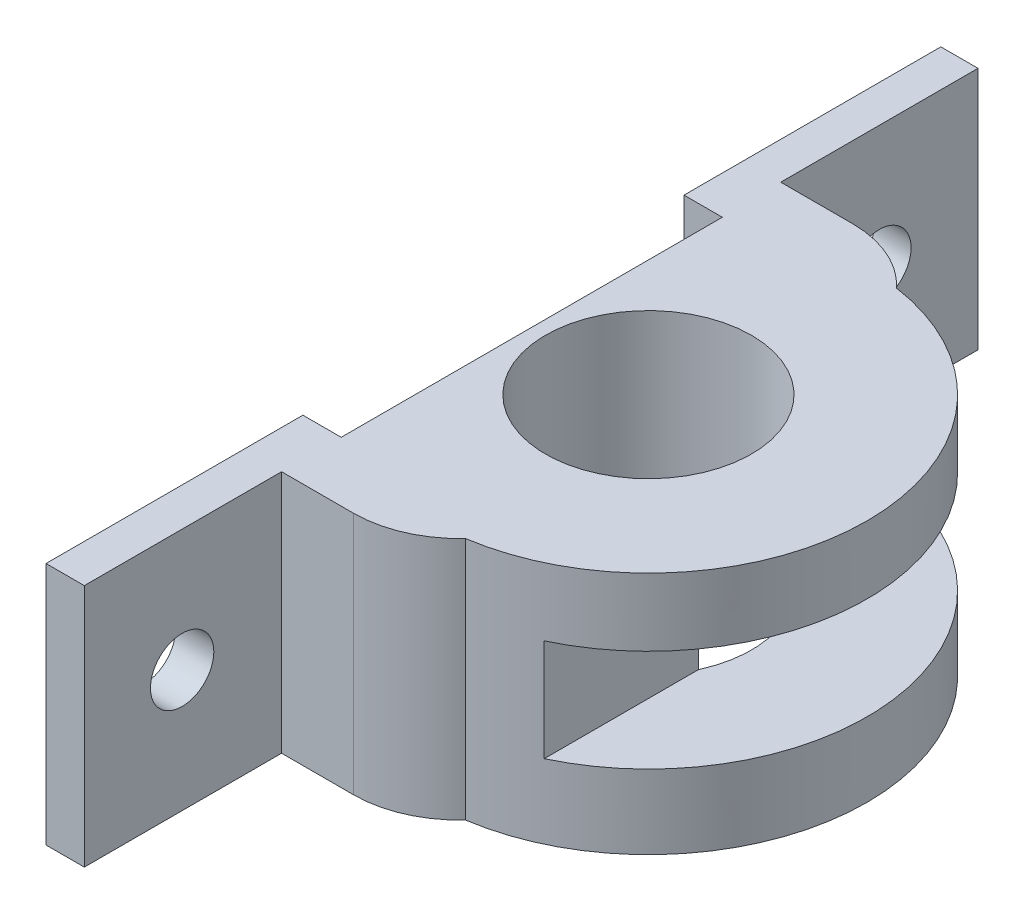
SolidWorks part; units mm, degrees
ref_plane "前基準面" through (0, 0, 0) normal (0, 0, 1) x (1, 0, 0)
ref_plane "上基準面" through (0, 0, 0) normal (0, 1, 0) x (1, 0, 0)
ref_plane "右基準面" through (0, 0, 0) normal (1, 0, 0) x (0, 0, -1)
sketch "草圖1" plane through (0, 0, 0) normal (0, 1, 0) x (1, 0, 0)
  circle A0 centre (0, 0) radius 9.68
  dimension "D1" = 19.36
extrude "伸長-薄件1" add sketch "草圖1" along normal blind 116.68 thin thin type one direction wall 11
ref_plane "平面1" through (-21, 0, 0) normal (1, 0, 0) x (0, 0, -1)
sketch "草圖11" plane through (0, 116.68, 0) normal (0, 1, 0) x (1, 0, 0)
  line L0 (-993.1634, -44.2358) -> (49006.8366, -44.2358) construction
  line L2 (35.2085, 30.7642) -> (8.2085, 30.7642)
  line L3 (35.2085, 30.7642) -> (35.2085, -119.2358)
  line L4 (35.2085, -119.2358) -> (8.2085, -119.2358)
  line L5 (8.2085, 30.7642) -> (8.2085, -119.2358)
  line L6 (35.2085, 30.7642) -> (8.2085, -119.2358) construction
  line L7 (35.2085, -119.2358) -> (8.2085, 30.7642) construction
  circle A0 centre (0, 0) radius 20.68 construction
  point P1 (21.7085, -44.2358)
  dimension "D1" = 150
  dimension "D2" = 27
  dimension "D3" = 30.7642
extrude "除料-伸長3" cut sketch "草圖11" against normal blind 40
ref_plane "平面2" through (0, 0, 21) normal (0, 0, 1) x (1, 0, 0)
sketch "草圖13" plane through (0, 0, 21) normal (0, 0, 1) x (1, 0, 0)
  line L0 (-21, -22.649) -> (-21, 22.649) construction
  line L1 (-21, 122.7847) -> (-11, 122.7847)
  line L2 (-21, 122.7847) -> (-21, -5.5603)
  line L3 (-21, -5.5603) -> (-11, -5.5603)
  line L4 (-11, 122.7847) -> (-11, -5.5603)
  dimension "D1" = 10
extrude "除料-伸長7" cut sketch "草圖13" against normal through all
sketch "草圖15" plane through (0, 0, 21) normal (0, 0, 1) x (1, 0, 0)
  line L0 (-1.3957, -883.32) -> (-1.3957, 49116.68) construction
  line L1 (8.2085, 116.68) -> (-11, 116.68) construction
  line L2 (-11, 0) -> (20.68, 0) construction
  line L3 (2.6043, 86.68) -> (-5.3957, 86.68)
  line L4 (2.6043, 86.68) -> (2.6043, 18)
  line L5 (2.6043, 18) -> (-5.3957, 18)
  line L6 (-5.3957, 86.68) -> (-5.3957, 18)
  line L7 (2.6043, 86.68) -> (-5.3957, 18) construction
  line L8 (2.6043, 18) -> (-5.3957, 86.68) construction
  point P1 (-1.3957, 52.34)
  point P5 (-1.3957, 116.68)
  dimension "D1" = 30
  dimension "D2" = 18
  dimension "D3" = 8
extrude "除料-伸長9" cut sketch "草圖15" against normal blind 48
sketch "草圖16" plane through (8.2085, 0, 0) normal (1, 0, 0) x (0, 0, -1)
  line L0 (20.68, 86.68) -> (20.68, 116.68) construction
  line L1 (5.1306, 116.68) -> (20.68, 116.68)
  line L2 (5.1306, 116.68) -> (5.1306, 96.68)
  line L3 (5.1306, 96.68) -> (20.68, 96.68)
  line L4 (20.68, 116.68) -> (20.68, 96.68)
  line L5 (-5.1306, 76.68) -> (-5.1306, 116.68) construction
  line L6 (-5.1306, 96.68) -> (-20.59, 96.68)
  line L7 (-5.1306, 96.68) -> (-5.1306, 116.68)
  line L8 (-5.1306, 116.68) -> (-20.59, 116.68)
  line L9 (-20.59, 96.68) -> (-20.59, 116.68)
  line L10 (-17.5118, 116.68) -> (-20.68, 116.68) construction
  dimension "D1" = 20
extrude "填料-伸長4" add sketch "草圖16" against normal blind 19.2
sketch "草圖17" plane through (0, 116.68, 0) normal (0, 1, 0) x (1, 0, 0)
  line L0 (-1009.59, 0) -> (48990.41, 0) construction
  line L1 (8.2085, 20.68) -> (8.2085, 5.1306) construction
  line L2 (8.2085, 6.97) -> (-11, 6.97)
  line L3 (8.2085, 6.97) -> (8.2085, -7.06)
  line L4 (8.2085, -7.06) -> (-11, -7.06)
  line L5 (-11, 6.97) -> (-11, -7.06)
  line L6 (-11, -17.5118) -> (-11, 17.5118) construction
  line L7 (-10.9915, -20.59) -> (-1.9273, -20.59) construction
  arc A0 (-8.2085, 5.1306) -> (-8.2085, -5.1306) centre (0, 0) ccw construction
  point P6 (-9.68, 0)
  dimension "D1" = 14.03
  dimension "D2" = 13.53
extrude "除料-伸長10" cut sketch "草圖17" against normal blind 20.2
sketch "草圖18" plane through (0, 0, 0) normal (0, -1, 0) x (1, 0, 0)
  circle A0 centre (0, 0) radius 9.59
extrude "除料-伸長11" cut sketch "草圖18" against normal through all
sketch "草圖21" plane through (0, 0, -20.68) normal (0, 0, -1) x (-1, 0, 0)
  line L0 (1.3915, 96.68) -> (1.3915, 105.73) construction
  line L1 (0, 96.68) -> (10.9915, 96.68) construction
  line L2 (1.3915, 105.73) -> (1.3915, 108.73) construction
  circle A0 centre (1.3915, 108.73) radius 2.985
  dimension "D3" = 5.97
  dimension "D1" = 9.05
  dimension "D2" = 3
extrude "除料-伸長12" cut sketch "草圖21" against normal blind 55.2
sketch "草圖23" plane through (0, 0, -20.68) normal (0, 0, -1) x (-1, 0, 0)
  line L0 (1.3915, 105.745) -> (1.3915, -11.785) construction
  circle A0 centre (1.3915, 108.73) radius 2.985 construction
  dimension "D1" = 117.53
sketch "草圖24" plane through (0, 0, 0) normal (0, -1, 0) x (1, 0, 0)
  circle A0 centre (0, 0) radius 9.59
extrude "伸長-薄件2" add sketch "草圖24" along normal blind 55.2 thin thin type one direction wall 11
sketch "草圖25" plane through (0, 0, 21) normal (0, 0, 1) x (1, 0, 0)
  line L0 (-1.3915, -11.785) -> (22.6124, -11.785)
  line L1 (22.6124, -11.785) -> (22.6124, -63.8733)
  line L2 (-22.7495, -63.8733) -> (22.6124, -63.8733)
  line L3 (-22.7495, -63.8733) -> (-22.7495, -11.785)
  line L4 (-22.7495, -11.785) -> (-1.3915, -11.785)
extrude "除料-伸長13" cut sketch "草圖25" against normal blind 55.2
sketch "草圖26" plane through (0, 0, 0) normal (0, 1, 0) x (1, 0, 0)
  line L0 (-21, -22.649) -> (-21, 22.649) construction
  line L1 (-10.9915, 20.68) -> (-21, 20.68)
  line L2 (-10.9915, 20.68) -> (-10.9915, -21)
  line L3 (-10.9915, -21) -> (-21, -21)
  line L4 (-21, 20.68) -> (-21, -21)
  line L5 (-17.6, -21) -> (17.6, -21) construction
extrude "除料-伸長15" cut sketch "草圖26" against normal blind 55.2
ref_plane "平面3" through (21, 0, 0) normal (1, 0, 0) x (0, 0, -1)
sketch "草圖27" plane through (21, 0, 0) normal (1, 0, 0) x (0, 0, -1)
  line L0 (0, -923.32) -> (0, 49076.68) construction
  line L1 (5.1306, 76.68) -> (-5.1306, 76.68) construction
  line L2 (18.9811, 76.68) -> (-18.9811, 76.68) construction
  line L3 (-5, 61.68) -> (5, 61.68)
  line L4 (-5, 61.68) -> (-5, 21.68)
  line L5 (-5, 21.68) -> (5, 21.68)
  line L6 (5, 61.68) -> (5, 21.68)
  line L7 (-5, 61.68) -> (5, 21.68) construction
  line L8 (-5, 21.68) -> (5, 61.68) construction
  point P1 (0, 41.68)
  point P5 (0, 76.68)
  dimension "D1" = 15
  dimension "D2" = 40
  dimension "D3" = 10
extrude "除料-伸長16" cut sketch "草圖27" against normal blind 55.2
sketch "草圖28" plane through (21, 0, 0) normal (1, 0, 0) x (0, 0, -1)
  line L1 (-22.4403, 4.804) -> (22.4403, 4.804)
  line L2 (-22.4403, 4.804) -> (-22.4403, -4.804)
  line L3 (-22.4403, -4.804) -> (22.4403, -4.804)
  line L4 (22.4403, 4.804) -> (22.4403, -4.804)
  line L5 (-22.4403, 4.804) -> (22.4403, -4.804) construction
  line L6 (-22.4403, -4.804) -> (22.4403, 4.804) construction
  point P0 (0, 0)
extrude "除料-伸長17" cut sketch "草圖28" against normal blind 12.2
sketch "草圖35" plane through (-10.9915, 0, 0) normal (-1, 0, 0) x (0, 0, 1)
  line L0 (20.59, 116.68) -> (20.59, 96.68)
  line L1 (20.59, 96.68) -> (7.06, 96.68)
  line L2 (7.06, 96.68) -> (7.06, 116.68)
  line L3 (7.06, 116.68) -> (20.59, 116.68)
extrude "填料-伸長10" add sketch "草圖35" along normal blind 15
sketch "草圖36" plane through (-10.9915, 0, 0) normal (-1, 0, 0) x (0, 0, 1)
  line L0 (-20.68, 116.68) -> (-6.97, 116.68)
  line L1 (-6.97, 116.68) -> (-6.97, 96.48)
  line L2 (-6.97, 96.48) -> (-20.68, 96.68)
  line L3 (-20.68, 96.68) -> (-20.68, 116.68)
extrude "填料-伸長11" add sketch "草圖36" along normal blind 15
sketch "草圖37" plane through (0, 0, 20.59) normal (0, 0, 1) x (1, 0, 0)
  line L0 (-25.9915, 96.68) -> (-1.9273, 96.68) construction
  line L1 (-25.9915, 116.68) -> (-16.9915, 116.68)
  line L2 (-25.9915, 116.68) -> (-25.9915, 96.68)
  line L3 (-25.9915, 96.68) -> (-16.9915, 96.68)
  line L4 (-16.9915, 116.68) -> (-16.9915, 96.68)
  dimension "D1" = 9
extrude "填料-伸長12" add sketch "草圖37" along normal blind 20
sketch "草圖38" plane through (0, 0, -20.68) normal (0, 0, -1) x (-1, 0, 0)
  line L0 (25.9915, 116.68) -> (-8.2085, 116.68) construction
  line L1 (25.9915, 96.68) -> (16.9915, 96.68)
  line L2 (25.9915, 96.68) -> (25.9915, 116.68)
  line L3 (25.9915, 116.68) -> (16.9915, 116.68)
  line L4 (16.9915, 96.68) -> (16.9915, 116.68)
  dimension "D1" = 9
extrude "填料-伸長13" add sketch "草圖38" along normal blind 20
sketch "草圖42" plane through (-16.9915, 0, 0) normal (1, 0, 0) x (0, 0, -1)
  line L0 (30.68, -903.32) -> (30.68, 49096.68) construction
  line L1 (40.68, 96.68) -> (20.68, 96.68) construction
  line L2 (-959.32, 106.68) -> (49040.68, 106.68) construction
  line L3 (40.68, 116.68) -> (40.68, 96.68) construction
  line L4 (-30.59, -903.32) -> (-30.59, 49096.68) construction
  line L5 (-40.59, 96.68) -> (-20.59, 96.68) construction
  circle A0 centre (30.68, 106.5544) radius 2.985
  circle A1 centre (-30.3956, 106.68) radius 2.985
  point P5 (30.68, 96.68)
  point P10 (40.68, 106.68)
  point P15 (-30.59, 96.68)
  dimension "D1" = 5.97
  dimension "D2" = 5.97
extrude "除料-伸長21" cut sketch "草圖42" against normal blind 20
sketch "草圖43" plane through (0, 116.68, 0) normal (0, 1, 0) x (1, 0, 0)
  line L0 (-11, 6.97) -> (-10.9915, 20.68)
  line L1 (-10.9915, 20.68) -> (-10.9915, 48.0968)
  line L2 (-10.9915, 48.0968) -> (-28.2748, 48.0968)
  line L3 (-28.2748, 48.0968) -> (-28.2748, -43.2705)
  line L4 (-28.2748, -43.2705) -> (-11, -43.2705)
  line L5 (-11, -43.2705) -> (-11, 6.97)
extrude "除料-伸長23" cut sketch "草圖43" against normal through all
sketch "草圖45" plane through (0, 0, 20.59) normal (0, 0, 1) x (1, 0, 0)
  line L0 (-11, 96.68) -> (-1.9273, 96.68) construction
  line L1 (-11, 116.68) -> (-8, 116.68)
  line L2 (-11, 116.68) -> (-11, 96.68)
  line L3 (-11, 96.68) -> (-8, 96.68)
  line L4 (-8, 116.68) -> (-8, 96.68)
  dimension "D1" = 3
extrude "填料-伸長14" add sketch "草圖45" along normal blind 30
sketch "草圖46" plane through (0, 0, -20.68) normal (0, 0, -1) x (-1, 0, 0)
  line L0 (0, 96.68) -> (10.9915, 96.68) construction
  line L1 (10.9915, 116.68) -> (7.9915, 116.68)
  line L2 (10.9915, 116.68) -> (10.9915, 96.68)
  line L3 (10.9915, 96.68) -> (7.9915, 96.68)
  line L4 (7.9915, 116.68) -> (7.9915, 96.68)
  dimension "D1" = 3
extrude "填料-伸長15" add sketch "草圖46" along normal blind 30
sketch "草圖47" plane through (-11, 0, 0) normal (-1, 0, 0) x (0, 0, 1)
  line L0 (50.59, 116.68) -> (7.06, 116.68) construction
  line L1 (50.59, 96.68) -> (17.5118, 96.68)
  line L2 (50.59, 96.68) -> (50.59, 116.68)
  line L3 (50.59, 116.68) -> (17.5118, 116.68)
  line L4 (17.5118, 96.68) -> (17.5118, 116.68)
extrude "填料-伸長16" add sketch "草圖47" along normal blind 50
sketch "草圖48" plane through (-10.9915, 0, 0) normal (-1, 0, 0) x (0, 0, 1)
  line L1 (-50.68, 116.68) -> (-20.68, 116.68)
  line L2 (-50.68, 116.68) -> (-50.68, 96.68)
  line L3 (-50.68, 96.68) -> (-20.68, 96.68)
  line L4 (-20.68, 116.68) -> (-20.68, 96.68)
extrude "填料-伸長17" add sketch "草圖48" along normal blind 50
sketch "草圖50" plane through (0, 0, 17.5118) normal (0, 0, -1) x (-1, 0, 0)
  line L0 (11, 96.68) -> (11, 116.68)
  line L1 (11, 116.68) -> (61, 116.68)
  line L2 (61, 116.68) -> (61, 96.68)
  line L3 (61, 96.68) -> (11, 96.68)
extrude "填料-伸長18" add sketch "草圖50" along normal blind 1
sketch "草圖51" plane through (0, 0, -20.68) normal (0, 0, 1) x (1, 0, 0)
  line L0 (-10.9915, 116.68) -> (-10.9915, 96.68)
  line L1 (-10.9915, 96.68) -> (-60.9915, 96.68)
  line L2 (-60.9915, 96.68) -> (-60.9915, 116.68)
  line L3 (-60.9915, 116.68) -> (-10.9915, 116.68)
extrude "填料-伸長19" add sketch "草圖51" along normal blind 1
sketch "草圖52" plane through (0, 116.68, 0) normal (0, 1, 0) x (1, 0, 0)
  line L0 (-34.4915, -949.32) -> (-34.4915, 49050.68) construction
  line L1 (-60.9915, 50.68) -> (-7.9915, 50.68) construction
  line L2 (-1007.9915, 35.68) -> (48992.0085, 35.68) construction
  line L3 (-7.9915, 50.68) -> (-7.9915, 20.68) construction
  line L4 (-60.9915, 19.68) -> (-60.9915, 50.68) construction
  line L5 (-7.9915, 50.68) -> (-60.9915, 50.68)
  line L6 (-7.9915, 50.68) -> (-7.9915, 36.68)
  line L7 (-7.9915, 36.68) -> (-60.9915, 36.68)
  line L8 (-60.9915, 50.68) -> (-60.9915, 36.68)
  point P5 (-34.4915, 50.68)
  point P10 (-7.9915, 35.68)
  dimension "D1" = 14
extrude "除料-伸長24" cut sketch "草圖52" against normal through all
sketch "草圖53" plane through (0, 116.68, 0) normal (0, 1, 0) x (1, 0, 0)
  line L0 (-61, -50.59) -> (-61, -16.5118) construction
  line L1 (-8, -50.59) -> (-61, -50.59)
  line L2 (-8, -50.59) -> (-8, -36.59)
  line L3 (-8, -36.59) -> (-61, -36.59)
  line L4 (-61, -50.59) -> (-61, -36.59)
  dimension "D1" = 14
extrude "除料-伸長25" cut sketch "草圖53" against normal through all
sketch "草圖54" plane through (0, 116.68, 0) normal (0, 1, 0) x (1, 0, 0)
  line L0 (-60.9915, 36.68) -> (-7.9915, 36.68) construction
  line L1 (-61, -36.59) -> (-21, -36.59)
  line L2 (-61, -36.59) -> (-61, 36.68)
  line L3 (-61, 36.68) -> (-21, 36.68)
  line L4 (-21, -36.59) -> (-21, 36.68)
  dimension "D1" = 40
extrude "除料-伸長26" cut sketch "草圖54" against normal through all
sketch "草圖55" plane through (0, 116.68, 0) normal (0, 1, 0) x (1, 0, 0)
  line L0 (-15.0276, -36.59) -> (-15.0276, -16.5118) construction
  line L1 (-8, -36.59) -> (-21, -36.59) construction
  line L2 (-21, -16.5118) -> (-11, -16.5118) construction
  line L3 (-13.4574, 19.68) -> (-13.4574, 39.76) construction
  line L4 (-10.9921, 19.68) -> (-21, 19.68) construction
  dimension "D1" = 20.08
sketch "草圖56" plane through (0, 0, -36.68) normal (0, 0, -1) x (-1, 0, 0)
  line L1 (7.9915, 96.68) -> (21, 96.68)
  line L2 (7.9915, 96.68) -> (7.9915, 116.68)
  line L3 (7.9915, 116.68) -> (21, 116.68)
  line L4 (21, 96.68) -> (21, 116.68)
extrude "填料-伸長21" add sketch "草圖56" along normal blind 3.08
ref_plane "平面4" through (0, 0, 50) normal (0, 0, 1) x (1, 0, 0)
sketch "草圖60" plane through (0, 116.68, 0) normal (0, 1, 0) x (1, 0, 0)
  line L0 (-21, 39.76) -> (-7.9915, 39.76) construction
  line L1 (-21, -36.59) -> (-14.4957, -36.59)
  line L2 (-21, -36.59) -> (-21, 39.76)
  line L3 (-21, 39.76) -> (-14.4957, 39.76)
  line L4 (-14.4957, -36.59) -> (-14.4957, 39.76)
extrude "除料-伸長30" cut sketch "草圖60" against normal through all
sketch "草圖61" plane through (0, 116.68, 0) normal (0, 1, 0) x (1, 0, 0)
  line L0 (1.9273, -20.59) -> (1.9273, -22.3991)
  line L1 (1.9273, -22.3991) -> (-2.1742, -21.4215)
  line L2 (-2.1742, -21.4215) -> (-2.1742, -20.59)
  line L3 (-8, -20.59) -> (-1.9273, -20.59) construction
  line L4 (-2.1742, -20.59) -> (1.9273, -20.59)
extrude "除料-伸長32" cut sketch "草圖61" against normal blind 20
sketch "草圖64" plane through (0, 116.68, 0) normal (0, 1, 0) x (1, 0, 0)
  line L1 (-8, -20.59) -> (8.2085, -20.59)
  line L2 (-8, -20.59) -> (-8, -20.68)
  line L3 (-8, -20.68) -> (8.2085, -20.68)
  line L4 (8.2085, -20.59) -> (8.2085, -20.68)
  dimension "D1" = 0.09
extrude "填料-伸長22" add sketch "草圖64" against normal blind 20
sketch "草圖65" plane through (0, 116.68, 0) normal (0, 1, 0) x (1, 0, 0)
  line L0 (-11, 6.97) -> (-10.9921, 19.68) construction
  line L1 (-11, -7.06) -> (-11, -16.5118) construction
  line L2 (-14.4957, -36.59) -> (-14.4957, -16.5118) construction
  line L3 (-11, -16.5118) -> (-14.4957, -16.5118)
  line L4 (-11, -16.5118) -> (-11, -19.7718)
  line L5 (-11, -19.7718) -> (-14.4957, -19.7718)
  line L6 (-14.4957, -16.5118) -> (-14.4957, -19.7718)
  dimension "D1" = 12.71
  dimension "D2" = 9.4518
  dimension "D3" = 3.26
extrude "除料-伸長33" cut sketch "草圖65" against normal through all
sketch "草圖66" plane through (0, 96.48, 0) normal (0, 1, 0) x (1, 0, 0)
  line L0 (-1011, -0.045) -> (48989, -0.045) construction
  line L1 (-11, 6.97) -> (-11, -7.06) construction
  line L2 (-12.9194, -0.045) -> (-12.9194, 17.905) construction
  line L3 (-12.9194, -0.045) -> (-12.9194, -17.995) construction
  line L4 (-11, -19.7718) -> (-11, -7.06) construction
  line L5 (-14.4957, -19.7718) -> (-11, -19.7718)
  line L6 (-14.4957, -19.7718) -> (-14.4957, -17.995)
  line L7 (-14.4957, -17.995) -> (-11, -17.995)
  line L8 (-11, -19.7718) -> (-11, -17.995)
  line L10 (-10.9921, 19.68) -> (-14.4957, 19.68)
  line L11 (-10.9921, 19.68) -> (-10.9921, 17.905)
  line L12 (-10.9921, 17.905) -> (-14.4957, 17.905)
  line L13 (-14.4957, 19.68) -> (-14.4957, 17.905)
  point P5 (-11, -0.045)
  dimension "D1" = 17.95
  dimension "D2" = 17.95
extrude "填料-伸長23" add sketch "草圖66" along normal blind 20.2
sketch "草圖68" plane through (0, 116.68, 0) normal (0, 1, 0) x (1, 0, 0)
  line L0 (-10.9932, 17.905) -> (-10.9932, 39.76) construction
  line L1 (-14.4957, 39.76) -> (-7.9915, 39.76) construction
  line L2 (-14.4957, 17.905) -> (-14.4957, 39.76) construction
  line L3 (-7.9915, 39.76) -> (-14.4957, 39.76)
  line L4 (-7.9915, 39.76) -> (-7.9915, 36.1)
  line L5 (-7.9915, 36.1) -> (-14.4957, 36.1)
  line L6 (-14.4957, 39.76) -> (-14.4957, 36.1)
  dimension "D1" = 3.66
extrude "除料-伸長34" cut sketch "草圖68" against normal blind 20
sketch "草圖69" plane through (-7.9915, 0, 0) normal (1, 0, 0) x (0, 0, -1)
  line L0 (28.39, -903.32) -> (28.39, 49096.68) construction
  line L1 (36.1, 96.68) -> (20.68, 96.68) construction
  line L2 (-28.635, -903.32) -> (-28.635, 49096.68) construction
  line L3 (-36.59, 96.68) -> (-20.68, 96.68) construction
  line L4 (-963.9, 106.68) -> (49036.1, 106.68) construction
  line L5 (36.1, 96.68) -> (36.1, 116.68) construction
  circle A0 centre (28.39, 106.68) radius 2.985
  circle A1 centre (-28.635, 106.68) radius 2.985
  point P5 (28.39, 96.68)
  point P10 (-28.635, 96.68)
  point P15 (36.1, 106.68)
  dimension "D1" = 5.97
  dimension "D2" = 5.97
extrude "除料-伸長35" cut sketch "草圖69" against normal through all
sketch "草圖70" plane through (0, 0, 20.59) normal (0, 0, -1) x (-1, 0, 0)
  circle A0 centre (1.3915, 108.73) radius 2.985
  dimension "D1" = 5.97
extrude "除料-伸長36" cut sketch "草圖70" against normal through all
sketch "草圖71" plane through (0, 0, 50) normal (0, 0, 1) x (1, 0, 0)
  line L1 (-16.2413, 123.1465) -> (21.764, 123.1465)
  line L2 (-16.2413, 123.1465) -> (-16.2413, 11.1806)
  line L3 (-16.2413, 11.1806) -> (21.764, 11.1806)
  line L4 (21.764, 123.1465) -> (21.764, 11.1806)
extrude "除料-伸長37" cut sketch "草圖71" against normal through all
sketch "草圖72" plane through (0, -11.785, 0) normal (0, -1, 0) x (1, 0, 0)
  circle A0 centre (0, 0) radius 9.7
  dimension "D1" = 19.4
extrude "除料-伸長38" cut sketch "草圖72" against normal through all
sketch "草圖77" plane through (0, 11.1806, 0) normal (0, 1, 0) x (1, 0, 0)
  circle A0 centre (0, 0) radius 20.59
  dimension "D1" = 41.18
extrude "除料-伸長-薄件2" cut sketch "草圖77" against normal blind 22 thin thin type one direction wall 10
sketch "草圖78" plane through (-11, 0, 0) normal (-1, 0, 0) x (0, 0, 1)
  line L1 (17.4054, 11.1806) -> (-17.4108, 11.1806)
  line L2 (17.4054, 11.1806) -> (17.4054, -11.785)
  line L3 (17.4054, -11.785) -> (-17.4108, -11.785)
  line L4 (-17.4108, 11.1806) -> (-17.4108, -11.785)
extrude "填料-伸長26" add sketch "草圖78" along normal blind 0.1
sketch "草圖80" plane through (0, -11.785, 0) normal (0, -1, 0) x (1, 0, 0)
  line L1 (-11.1, -17.4108) -> (-14, -17.4108)
  line L2 (-11.1, -17.4108) -> (-11.1, -23.5595)
  line L3 (-11.1, -23.5595) -> (-14, -23.5595)
  line L4 (-14, -17.4108) -> (-14, -23.5595)
extrude "填料-伸長28" add sketch "草圖80" against normal blind 23.1 separate body
sketch "草圖81" plane through (-11.1, 0, 0) normal (1, 0, 0) x (0, 0, -1)
  line L0 (17.4108, -11.785) -> (23.5595, -11.785)
  line L1 (23.5595, -11.785) -> (23.5595, 11.315)
  line L2 (23.5595, 11.315) -> (17.4108, 11.315)
  line L3 (17.4108, 11.315) -> (17.4108, -11.785)
extrude "填料-伸長29" add sketch "草圖81" along normal blind 14.1
sketch "草圖82" plane through (3, 0, 0) normal (1, 0, 0) x (0, 0, -1)
  line L0 (17.4108, 11.1806) -> (17.4108, 11.315)
  line L1 (17.4108, 11.315) -> (23.5595, 11.315)
  line L2 (23.5595, 11.315) -> (23.5595, 11.1806)
  line L3 (23.5595, -11.785) -> (23.5595, 11.315) construction
  line L4 (23.5595, 11.1806) -> (17.4108, 11.1806)
extrude "除料-伸長39" cut sketch "草圖82" against normal blind 19.1
sketch "草圖83" plane through (0, 0, -17.4108) normal (0, 0, 1) x (1, 0, 0)
  line L1 (-11.1, 11.1806) -> (-14, 11.1806)
  line L2 (-11.1, 11.1806) -> (-11.1, -11.785)
  line L3 (-11.1, -11.785) -> (-14, -11.785)
  line L4 (-14, 11.1806) -> (-14, -11.785)
extrude "填料-伸長30" add sketch "草圖83" against normal blind 19.1
fillet "圓角1" radius 10 1 edges at (3, -0.3022, -23.5595)
sketch "草圖84" plane through (0, -11.785, 0) normal (0, -1, 0) x (-1, 0, 0)
  line L1 (11.1, 17.4108) -> (14.6, 17.4108)
  line L2 (11.1, 17.4108) -> (11.1, 36.5108)
  line L3 (11.1, 36.5108) -> (14.6, 36.5108)
  line L4 (14.6, 17.4108) -> (14.6, 36.5108)
  dimension "D1" = 3.5
extrude "填料-伸長31" add sketch "草圖84" against normal blind 23.1
sketch "草圖85" plane through (0, -11.785, 0) normal (0, -1, 0) x (1, 0, 0)
  line L0 (-11.1, -17.4108) -> (-11.1, -35.9908) construction
  line L1 (-11.1, -36.5108) -> (-11.1, -23.5595) construction
  line L3 (-11.1, -35.9908) -> (-14.6, -35.9908)
  line L4 (-11.1, -35.9908) -> (-11.1, -36.5108)
  line L5 (-11.1, -36.5108) -> (-14.6, -36.5108)
  line L6 (-14.6, -35.9908) -> (-14.6, -36.5108)
  dimension "D1" = 18.58
extrude "除料-伸長40" cut sketch "草圖85" against normal through all
sketch "草圖86" plane through (0, 0, -17.4108) normal (0, 0, 1) x (1, 0, 0)
  line L1 (-11.1, 11.1806) -> (-14.6, 11.1806)
  line L2 (-11.1, 11.1806) -> (-11.1, -11.785)
  line L3 (-11.1, -11.785) -> (-14.6, -11.785)
  line L4 (-14.6, 11.1806) -> (-14.6, -11.785)
extrude "填料-伸長32" add sketch "草圖86" along normal blind 62.1
sketch "草圖87" plane through (0, -11.785, 0) normal (0, -1, 0) x (1, 0, 0)
  line L0 (-14.6, 44.6892) -> (-14.6, -35.9908) construction
  line L1 (-10.9915, -17.4108) -> (-14.6, -17.4108)
  line L2 (-10.9915, -17.4108) -> (-10.9915, 17.4054)
  line L3 (-10.9915, 17.4054) -> (-14.6, 17.4054)
  line L4 (-14.6, -17.4108) -> (-14.6, 17.4054)
extrude "除料-伸長41" cut sketch "草圖87" against normal blind 62.1
sketch "草圖89" plane through (0, -11.785, 0) normal (0, -1, 0) x (1, 0, 0)
  line L0 (-10.9915, 17.4108) -> (-10.9915, 23.5608) construction
  line L1 (-11.1, 44.6892) -> (-11.1, 17.4054) construction
  line L2 (-11.1, 23.5608) -> (-10.9915, 23.5608)
  line L3 (-11.1, 23.5608) -> (-11.1, 17.4108)
  line L4 (-11.1, 17.4108) -> (-10.9915, 17.4108)
  line L5 (-10.9915, 23.5608) -> (-10.9915, 17.4108)
  dimension "D1" = 6.15
extrude "填料-伸長33" add sketch "草圖89" against normal blind 23.1
sketch "草圖90" plane through (0, 0, 23.5608) normal (0, 0, 1) x (1, 0, 0)
  line L0 (-11, 11.1806) -> (-11.1, 11.1806)
  line L1 (-11.1, 11.1806) -> (-11.1, -11.785)
  line L2 (-11.1, -11.785) -> (-10.9915, -11.785)
  line L3 (-10.9915, -11.785) -> (-10.9915, 11.1806)
  line L4 (-10.9915, 11.1806) -> (-11, 11.1806)
extrude "填料-伸長34" add sketch "草圖90" along normal blind 22.1
sketch "草圖91" plane through (-11.1, 0, 0) normal (-1, 0, 0) x (0, 0, 1)
  line L1 (45.6608, -11.785) -> (44.6892, -11.785)
  line L2 (45.6608, -11.785) -> (45.6608, 11.1806)
  line L3 (45.6608, 11.1806) -> (44.6892, 11.1806)
  line L4 (44.6892, -11.785) -> (44.6892, 11.1806)
extrude "除料-伸長42" cut sketch "草圖91" against normal blind 22.1
sketch "草圖93" plane through (0, -11.785, 0) normal (0, -1, 0) x (1, 0, 0)
  line L0 (-10.9915, 17.4108) -> (-10.9915, 23.5608) construction
  line L1 (-10.9915, 17.4108) -> (-10.9915, 44.6892) construction
  dimension "D1" = 6.15
sketch "草圖94" plane through (-10.9915, 0, 0) normal (1, 0, 0) x (0, 0, -1)
  line L0 (-23.5608, -11.785) -> (-23.5608, 11.1806) construction
  line L1 (-17.4108, -11.785) -> (-23.5608, -11.785) construction
sketch "草圖95" plane through (-10.9915, 0, 0) normal (1, 0, 0) x (0, 0, -1)
  line L1 (-23.5608, 11.1806) -> (-17.4108, 11.1806)
  line L2 (-17.4108, 11.315) -> (-17.4108, -11.785) construction
  line L3 (-17.4108, 11.1806) -> (-17.4108, -11.785)
  line L4 (-17.4108, -11.785) -> (-23.5608, -11.785)
  line L5 (-23.5608, -11.785) -> (-23.5608, 11.1806)
extrude "填料-伸長35" add sketch "草圖95" along normal blind 14.1
fillet "圓角2" radius 10 1 edges at (3.1085, -0.3022, 23.5608)
sketch "草圖96" plane through (0, -11.785, 0) normal (0, -1, 0) x (1, 0, 0)
  line L0 (-10.9915, 23.5608) -> (-10.9915, 42.1408) construction
  line L1 (-10.9915, 23.5608) -> (-10.9915, 44.6892) construction
  line L3 (-10.9915, 42.1408) -> (-14.6, 42.1408)
  line L4 (-10.9915, 42.1408) -> (-10.9915, 44.6892)
  line L5 (-10.9915, 44.6892) -> (-14.6, 44.6892)
  line L6 (-14.6, 42.1408) -> (-14.6, 44.6892)
  dimension "D1" = 18.58
extrude "除料-伸長43" cut sketch "草圖96" against normal through all
sketch "草圖97" plane through (0, -11.785, 0) normal (0, -1, 0) x (1, 0, 0)
  line L0 (-11.1, -23.5595) -> (-11.1, -42.1395) construction
  line L2 (-14.6, -35.9908) -> (-11.1, -35.9908)
  line L3 (-14.6, -35.9908) -> (-14.6, -42.1395)
  line L4 (-14.6, -42.1395) -> (-11.1, -42.1395)
  line L5 (-11.1, -35.9908) -> (-11.1, -42.1395)
  dimension "D1" = 18.58
extrude "填料-伸長36" add sketch "草圖97" against normal blind 23.1
sketch "草圖98" plane through (-11.1, 0, 0) normal (1, 0, 0) x (0, 0, -1)
  line L0 (17.4108, 11.1806) -> (17.4108, 11.315)
  line L1 (17.4108, 11.315) -> (22.1983, 11.315)
  line L2 (42.1395, 11.315) -> (17.4108, 11.315) construction
  line L3 (22.1983, 11.315) -> (38.4617, 11.315)
  line L4 (38.4617, 11.315) -> (42.1395, 11.315)
  line L5 (42.1395, 11.315) -> (42.1395, 11.1806)
  line L6 (42.1395, 11.315) -> (42.1395, -11.785) construction
  line L7 (42.1395, 11.1806) -> (17.4108, 11.1806)
extrude "除料-伸長44" cut sketch "草圖98" against normal blind 23.1
sketch "草圖99" plane through (-10.9915, 0, 0) normal (1, 0, 0) x (0, 0, -1)
  line L1 (-23.5608, 11.1806) -> (-17.4108, 11.1806)
  line L2 (-23.5608, 11.1806) -> (-23.5608, 11.315)
  line L3 (-23.5608, 11.315) -> (-17.4108, 11.315)
  line L4 (-17.4108, 11.1806) -> (-17.4108, 11.315)
extrude "除料-伸長45" cut sketch "草圖99" against normal blind 23.1
sketch "草圖100" plane through (-10.9915, 0, 0) normal (1, 0, 0) x (0, 0, -1)
  line L0 (-1042.1408, -0.3022) -> (48957.8592, -0.3022) construction
  line L1 (-42.1408, 11.1806) -> (-42.1408, -11.785) construction
  line L2 (-32.8508, -988.8194) -> (-32.8508, 49011.1806) construction
  line L3 (-42.1408, 11.1806) -> (-23.5608, 11.1806) construction
  line L4 (32.8495, -988.8194) -> (32.8495, 49011.1806) construction
  line L5 (23.5595, 11.1806) -> (42.1395, 11.1806) construction
  point P5 (-42.1408, -0.3022)
  point P10 (-32.8508, 11.1806)
  point P15 (32.8495, 11.1806)
sketch "草圖101" plane through (-10.9915, 0, 0) normal (1, 0, 0) x (0, 0, -1)
  line L0 (-201042.1408, -0.3022) -> (248957.8592, -0.3022) construction
  line L1 (32.8495, -200988.8194) -> (32.8495, 249011.1806) construction
  circle A0 centre (-32.9287, -0.3022) radius 2.985
  circle A1 centre (32.8495, -0.3022) radius 2.985
  dimension "D1" = 5.97
  dimension "D2" = 5.97
extrude "除料-伸長46" cut sketch "草圖101" against normal blind 23.1
sketch "草圖102" plane through (0, 11.1806, 0) normal (0, 1, 0) x (1, 0, 0)
  line L0 (-14.6, 42.1395) -> (-14.6, 17.4108) construction
  line L1 (-10.9915, 17.4108) -> (-14.6, 17.4108)
  line L2 (-10.9915, 17.4108) -> (-10.9915, 17.9508)
  line L3 (-10.9915, 17.9508) -> (-14.6, 17.9508)
  line L4 (-14.6, 17.4108) -> (-14.6, 17.9508)
  line L5 (-14.6, -42.1408) -> (-14.6, -17.4054) construction
  line L6 (-10.9915, -17.4108) -> (-14.6, -17.4108)
  line L7 (-10.9915, -17.4108) -> (-10.9915, -17.9508)
  line L8 (-10.9915, -17.9508) -> (-14.6, -17.9508)
  line L9 (-14.6, -17.4108) -> (-14.6, -17.9508)
  dimension "D1" = 0.54
  dimension "D2" = 0.54
sketch "草圖103" plane through (0, 11.1806, 0) normal (0, 1, 0) x (1, 0, 0)
  line L0 (-14.6, -17.4108) -> (-14.6, -17.9508) construction
  line L1 (-10.9915, -17.4054) -> (-14.6, -17.4054)
  line L2 (-10.9915, -17.4054) -> (-10.9915, -17.9454)
  line L3 (-10.9915, -17.9454) -> (-14.6, -17.9454)
  line L4 (-14.6, -17.4054) -> (-14.6, -17.9454)
  dimension "D1" = 0.54
extrude "除料-伸長49" cut sketch "草圖103" against normal through all
sketch "草圖104" plane through (0, 11.1806, 0) normal (0, 1, 0) x (1, 0, 0)
  line L0 (-14.6, 42.1395) -> (-14.6, 17.4108) construction
  line L1 (-10.9915, 17.4108) -> (-14.6, 17.4108)
  line L2 (-10.9915, 17.4108) -> (-10.9915, 17.9508)
  line L3 (-10.9915, 17.9508) -> (-14.6, 17.9508)
  line L4 (-14.6, 17.4108) -> (-14.6, 17.9508)
  dimension "D1" = 0.54
extrude "除料-伸長50" cut sketch "草圖104" against normal through all
